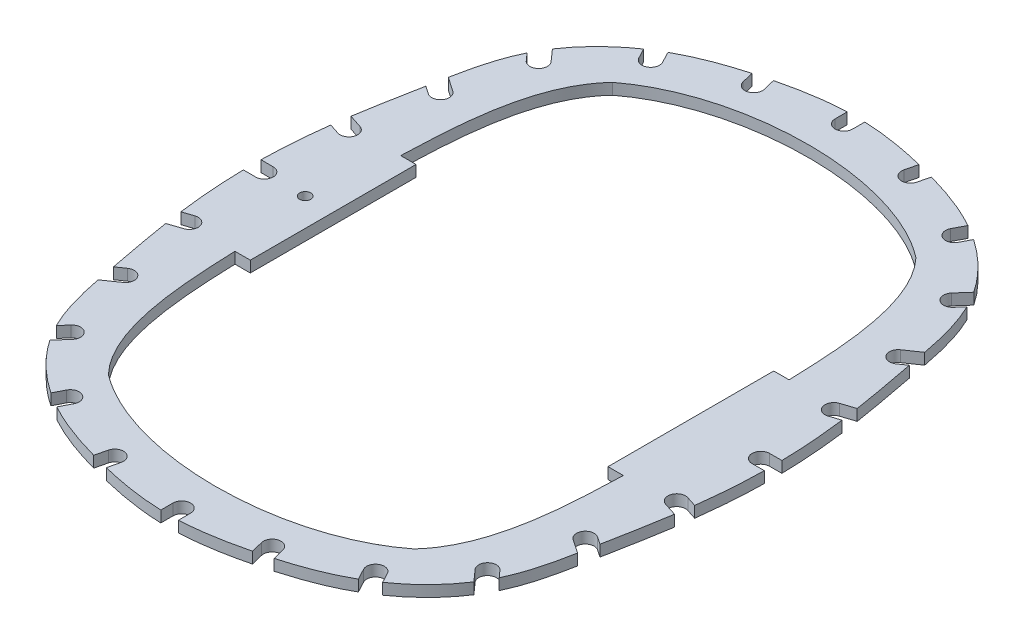
SolidWorks part; units mm, degrees
ref_plane "Front Plane" through (0, 0, 0) normal (0, 0, 1) x (1, 0, 0)
ref_plane "Top Plane" through (0, 0, 0) normal (0, 1, 0) x (1, 0, 0)
ref_plane "Right Plane" through (0, 0, 0) normal (1, 0, 0) x (0, 0, -1)
sketch "MainControlPoints" plane through (0, 0, 0) normal (0, 1, 0) x (1, 0, 0)
  line L1 (0, 188.5) -> (0, 0) construction
  line L2 (-44.5, 181.8105) -> (44.5, 181.8105) construction
  line L9 (-141, 0) -> (141, 0) construction
  line L10 (-86.25, 165.0195) -> (86.25, 165.0195) construction
  line L11 (-117.5, 132.6399) -> (117.5, 132.6399) construction
  line L12 (-130, 89.4108) -> (130, 89.4108) construction
  line L13 (-137.75, 45.0832) -> (137.75, 45.0832) construction
  spline S0 degree 3 poles (-44.8235, 182.8439) (0, 191.3281) (44.8235, 182.8439) (87.706, 168.1591) (121.8523, 134.6364) (129.8847, 89.1344) (138.6218, 45.2258) (142.1917, 0) (138.6218, -45.2258) (129.8847, -89.1344) (121.8523, -134.6364) (87.706, -168.1591) (44.8235, -182.8439) (0, -191.3281) (-44.8235, -182.8439) (-87.706, -168.1591) (-121.8523, -134.6364) (-129.8847, -89.1344) (-138.6218, -45.2258) (-142.1917, 0) (-138.6218, 45.2258) (-129.8847, 89.1344) (-121.8523, 134.6364) (-87.706, 168.1591) (-44.8235, 182.8439) (0, 191.3281) (44.8235, 182.8439) knots -0.124907 -0.083272 -0.041636 0 0.041636 0.083272 0.124907 0.166543 0.208179 0.25 0.291821 0.333457 0.375093 0.416728 0.458364 0.5 0.541636 0.583272 0.624907 0.666543 0.708179 0.75 0.791821 0.833457 0.875093 0.916728 0.958364 1 1.041636 1.083272 1.124907 only from (0, 188.5) to (0, 188.5)
  point P4 (0, 181.8105)
  point P7 (0, 0)
  point P8 (141, 0)
  point P9 (-141, 0)
  point P11 (44.5, 181.8105)
  point P14 (86.25, 165.0195)
  point P15 (0, 165.0195)
  point P16 (117.5, 132.6399)
  point P17 (130, 89.4108)
  point P18 (-44.5, 181.8105)
  point P19 (-86.25, 165.0195)
  point P20 (-117.5, 132.6399)
  point P23 (0, 132.6399)
  point P24 (137.75, 45.0832)
  point P25 (-130, 89.4108)
  point P26 (-137.75, 45.0832)
  point P27 (0, 188.5)
  point P30 (0, 89.4108)
  point P33 (0, 45.0832)
  point P34 (137.75, -45.0832)
  point P35 (130, -89.4108)
  point P36 (117.5, -132.6399)
  point P37 (86.25, -165.0195)
  point P38 (44.5, -181.8105)
  point P39 (0, -188.5)
  point P40 (-44.5, -181.8105)
  point P41 (-86.25, -165.0195)
  point P42 (-117.5, -132.6399)
  point P43 (-130, -89.4108)
  point P44 (-137.75, -45.0832)
  dimension "D3" = 282
  dimension "D2" = 188.5
  dimension "D5" = 45
  dimension "D6" = 45
  dimension "D1" = 89
  dimension "D4" = 172.5
  dimension "D7" = 45
  dimension "D8" = 235
  dimension "D9" = 45
  dimension "D10" = 260
  dimension "D11" = 45
  dimension "D12" = 275.5
ref_axis "Axis1" through (0, 0, -188.5) along (0, 1, 0)
ref_axis "Axis2" through (44.5, 0, -181.8105) along (0, 1, 0)
ref_axis "Axis3" through (86.25, 0, -165.0195) along (0, 1, 0)
ref_axis "Axis4" through (117.5, 0, -132.6399) along (0, 1, 0)
ref_axis "Axis5" through (130, 0, -89.4108) along (0, 1, 0)
ref_axis "Axis6" through (137.75, 0, -45.0832) along (0, 1, 0)
ref_axis "Axis7" through (141, 0, 0) along (0, 1, 0)
ref_axis "Axis8" through (137.75, 0, 45.0832) along (0, 1, 0)
ref_axis "Axis9" through (130, 0, 89.4108) along (0, 1, 0)
ref_axis "Axis10" through (117.5, 0, 132.6399) along (0, 1, 0)
ref_axis "Axis11" through (86.25, 0, 165.0195) along (0, 1, 0)
ref_axis "Axis12" through (44.5, 0, 181.8105) along (0, 1, 0)
ref_axis "Axis13" through (0, 0, 188.5) along (0, 1, 0)
ref_axis "Axis14" through (-44.5, 0, 181.8105) along (0, 1, 0)
ref_axis "Axis15" through (-86.25, 0, 165.0195) along (0, 1, 0)
ref_axis "Axis16" through (-117.5, 0, 132.6399) along (0, 1, 0)
ref_axis "Axis17" through (-130, 0, 89.4108) along (0, 1, 0)
ref_axis "Axis18" through (-137.75, 0, 45.0832) along (0, 1, 0)
ref_axis "Axis19" through (-141, 0, 0) along (0, 1, 0)
ref_axis "Axis20" through (-137.75, 0, -45.0832) along (0, 1, 0)
ref_axis "Axis21" through (-130, 0, -89.4108) along (0, 1, 0)
ref_axis "Axis22" through (-117.5, 0, -132.6399) along (0, 1, 0)
ref_axis "Axis23" through (-86.25, 0, -165.0195) along (0, 1, 0)
ref_axis "Axis24" through (-44.5, 0, -181.8105) along (0, 1, 0)
sketch "Sketch3" plane through (0, 0, 0) normal (0, 1, 0) x (1, 0, 0)
  spline S2 degree 3 poles (44.8235, 182.8439) (0, 191.3281) (-44.8235, 182.8439) (-87.706, 168.1591) (-121.8523, 134.6364) (-129.8847, 89.1344) (-138.6218, 45.2258) (-142.1917, 0) (-138.6218, -45.2258) (-129.8847, -89.1344) (-121.8523, -134.6364) (-87.706, -168.1591) (-44.8235, -182.8439) (0, -191.3281) (44.8235, -182.8439) (87.706, -168.1591) (121.8523, -134.6364) (129.8847, -89.1344) (138.6218, -45.2258) (142.1917, 0) (138.6218, 45.2258) (129.8847, 89.1344) (121.8523, 134.6364) (87.706, 168.1591) (44.8235, 182.8439) (0, 191.3281) (-44.8235, 182.8439) knots -0.124907 -0.083272 -0.041636 0 0.041636 0.083272 0.124907 0.166543 0.208179 0.25 0.291821 0.333457 0.375093 0.416728 0.458364 0.5 0.541636 0.583272 0.624907 0.666543 0.708179 0.75 0.791821 0.833457 0.875093 0.916728 0.958364 1 1.041636 1.083272 1.124907 only from (0, 188.5) to (0, 188.5)
  spline S3 degree 3 poles (44.8235, 182.8439) (0, 191.3281) (-44.8235, 182.8439) (-87.706, 168.1591) (-121.8523, 134.6364) (-129.8847, 89.1344) (-138.6218, 45.2258) (-142.1917, 0) (-138.6218, -45.2258) (-129.8847, -89.1344) (-121.8523, -134.6364) (-87.706, -168.1591) (-44.8235, -182.8439) (0, -191.3281) (44.8235, -182.8439) (87.706, -168.1591) (121.8523, -134.6364) (129.8847, -89.1344) (138.6218, -45.2258) (142.1917, 0) (138.6218, 45.2258) (129.8847, 89.1344) (121.8523, 134.6364) (87.706, 168.1591) (44.8235, 182.8439) (0, 191.3281) (-44.8235, 182.8439) knots -0.124907 -0.083272 -0.041636 0 0.041636 0.083272 0.124907 0.166543 0.208179 0.25 0.291821 0.333457 0.375093 0.416728 0.458364 0.5 0.541636 0.583272 0.624907 0.666543 0.708179 0.75 0.791821 0.833457 0.875093 0.916728 0.958364 1 1.041636 1.083272 1.124907 only from (0, 188.5) to (0, 188.5)
  dimension "D1" = 0
extrude "MainBody" add sketch "Sketch3" along normal blind 6.35
sketch "Sketch13" plane through (0, 6.35, 0) normal (0, 1, 0) x (1, 0, 0)
  spline S2 degree 3 poles (-0.0923, -195.5) (5.9061, -195.5) (11.7392, -195.085) (23.2981, -193.6453) (29.0237, -192.6199) (37.5559, -190.7615) (40.3905, -190.0886) (46.0447, -188.657) (48.8649, -187.9023) (53.0829, -186.6998) (54.4867, -186.2866) (57.2893, -185.4316) (58.6882, -184.9896) (62.8604, -183.6197) (65.6138, -182.6462) (73.7714, -179.5048) (79.0728, -177.1157) (86.7462, -172.933) (89.2575, -171.4385) (92.9463, -169.029) (94.1653, -168.1965) (96.5575, -166.4889) (97.7326, -165.6128) (101.1944, -162.9177) (103.4182, -161.032) (107.6923, -157.0772) (109.7427, -155.0081) (112.678, -151.7562) (113.633, -150.6474) (115.0284, -148.9451) (115.4873, -148.3711) (116.3925, -147.2097) (116.8393, -146.6213) (119.0306, -143.6582) (120.6466, -141.2209) (123.5916, -136.206) (124.9153, -133.6259) (127.2923, -128.3337) (128.3485, -125.623) (129.7723, -121.4785) (130.2202, -120.084) (131.0691, -117.272) (131.4694, -115.8571) (132.6042, -111.6095) (133.2755, -108.7656) (134.5145, -103.0626) (135.0819, -100.2036) (136.1775, -94.48) (136.707, -91.6156) (138.3251, -83.0265) (139.4215, -77.303) (141.5293, -65.8438) (142.5403, -60.108) (143.9035, -51.4821) (144.3323, -48.6031) (145.1247, -42.8358) (145.4885, -39.9475) (147.1362, -25.4811) (147.9101, -13.8294) (148.003, -0.6092) (148.0024, 0.8623) (147.9792, 3.8019) (147.9568, 5.2701) (147.8578, 9.6699) (147.7498, 12.5969) (147.3068, 21.3604) (146.8533, 27.1792) (145.6651, 38.7754) (144.9284, 44.5524) (143.2126, 56.0705) (142.2389, 61.8124) (140.1775, 73.2794) (139.0901, 79.0044) (137.4645, 87.5929) (136.9262, 90.4562) (135.8531, 96.1835) (135.3122, 99.0464) (133.5786, 107.6189) (132.2779, 113.3124) (130.1353, 120.3529) (129.6824, 121.7514) (128.7233, 124.5187) (128.2169, 125.8886) (126.6073, 129.9525) (125.4138, 132.6004) (122.7385, 137.7496) (121.2544, 140.2496) (118.8215, 143.8945) (117.9761, 145.0919) (116.2177, 147.4523) (115.3033, 148.6168) (112.4942, 152.0199) (110.5242, 154.1827) (106.4077, 158.3162) (104.2612, 160.2869) (99.8013, 164.0465) (97.4878, 165.8355) (93.8939, 168.384) (92.6724, 169.2128) (90.2027, 170.8151) (88.9554, 171.5879) (82.6598, 175.3171) (77.4348, 177.8708) (66.7035, 182.3362) (61.1969, 184.2476) (54.1978, 186.3725) (52.791, 186.7846) (49.9736, 187.5842) (48.5634, 187.9716) (44.3294, 189.1029) (41.5021, 189.818) (33.0032, 191.8167) (27.3144, 192.953) (15.8708, 194.6608) (10.1162, 195.2328) (1.4182, 195.5241) (-1.4925, 195.5238) (-7.3372, 195.3237) (-10.2708, 195.1267) (-14.6866, 194.6996) (-16.1609, 194.5352) (-19.0943, 194.1679) (-20.556, 193.9647) (-24.9277, 193.3015) (-27.824, 192.7881) (-36.4681, 191.071) (-42.1715, 189.6926) (-53.5026, 186.6371) (-59.1262, 184.9441) (-66.0624, 182.4605) (-67.445, 181.9454) (-70.1997, 180.8739) (-71.5737, 180.3168) (-75.6639, 178.5832) (-78.3432, 177.3468) (-83.5935, 174.6901) (-86.1644, 173.2698) (-91.1858, 170.2243) (-93.6357, 168.5985) (-97.2169, 166.0005) (-98.395, 165.108) (-100.7189, 163.2682) (-101.8655, 162.32) (-105.2234, 159.4186) (-107.3637, 157.4004) (-111.4418, 153.191) (-113.3796, 150.9998) (-117.0378, 146.4319) (-118.7583, 144.0551) (-121.1568, 140.3344) (-121.9259, 139.0681) (-123.0304, 137.1268) (-123.3898, 136.4736) (-124.087, 135.1618) (-124.4255, 134.5022) (-126.0692, 131.1868) (-127.2294, 128.4785) (-130.3408, 120.2205) (-131.9223, 114.5371) (-134.5909, 102.9918) (-135.6643, 97.1921) (-137.8355, 85.5987) (-138.9477, 79.8043) (-141.1029, 68.2094) (-142.1451, 62.4088) (-143.5618, 53.6948) (-144.0097, 50.788) (-144.8419, 44.9686) (-145.2255, 42.056) (-146.97, 27.4776) (-147.815, 15.7657) (-148.0521, -1.8942) (-147.9538, -7.7967) (-147.4225, -19.6316) (-146.9909, -25.5639) (-146.1143, -34.4827) (-145.7838, -37.4592) (-145.0527, -43.3941) (-144.6515, -46.3556) (-143.3516, -55.2244) (-142.36, -61.1163) (-140.253, -72.8796) (-139.1381, -78.7512) (-137.4708, -87.5593) (-136.9189, -90.496) (-135.8181, -96.3698) (-135.2627, -99.3053) (-133.4794, -108.0788) (-132.1352, -113.8842) (-129.4893, -122.4151) (-128.5024, -125.2292) (-126.8117, -129.3912) (-126.2131, -130.7686) (-125.2553, -132.818) (-124.9263, -133.498) (-124.2516, -134.843) (-123.9056, -135.5092) (-122.1306, -138.8075) (-120.5688, -141.343) (-117.1925, -146.2303) (-115.378, -148.582) (-111.5149, -153.1153) (-109.4647, -155.2983) (-105.1449, -159.494) (-102.9036, -161.4797) (-95.9543, -167.1259) (-91.0211, -170.4758) (-84.4967, -174.1698) (-83.1716, -174.8856) (-80.5028, -176.2632) (-79.1594, -176.925) (-75.1047, -178.8358) (-72.3686, -180.0105) (-64.0786, -183.2871) (-58.4429, -185.1422) (-49.8888, -187.6214) (-47.0211, -188.3984) (-41.2605, -189.8765) (-38.3664, -190.5739) (-32.5429, -191.862) (-29.6099, -192.4531) (-23.735, -193.4975) (-20.7901, -193.9515) (-14.8831, -194.699) (-11.9208, -194.9924) (-7.4624, -195.2928) (-5.9738, -195.3696) (-3.7367, -195.4473) (-2.6172, -195.4768) (-1.3092, -195.4942) (-0.6548, -195.4985) (-0.3742, -195.4995) (-0.1871, -195.4999) (-0.0923, -195.5) (5.9061, -195.5) (11.7392, -195.085) knots -0.000244 -0.000244 0 0 0.015625 0.015625 0.03125 0.03125 0.039063 0.039063 0.046875 0.046875 0.050781 0.050781 0.054688 0.054688 0.0625 0.0625 0.078125 0.078125 0.085938 0.085938 0.089844 0.089844 0.09375 0.09375 0.101563 0.101563 0.109375 0.109375 0.113281 0.113281 0.115234 0.115234 0.117188 0.117188 0.125 0.125 0.132813 0.132813 0.140625 0.140625 0.144531 0.144531 0.148438 0.148438 0.15625 0.15625 0.164063 0.164063 0.171875 0.171875 0.1875 0.1875 0.203125 0.203125 0.210938 0.210938 0.21875 0.21875 0.25 0.25 0.253906 0.253906 0.257813 0.257813 0.265625 0.265625 0.28125 0.28125 0.296875 0.296875 0.3125 0.3125 0.328125 0.328125 0.335938 0.335938 0.34375 0.34375 0.359375 0.359375 0.363281 0.363281 0.367188 0.367188 0.375 0.375 0.382813 0.382813 0.386719 0.386719 0.390625 0.390625 0.398438 0.398438 0.40625 0.40625 0.414063 0.414063 0.417969 0.417969 0.421875 0.421875 0.4375 0.4375 0.453125 0.453125 0.457031 0.457031 0.460938 0.460938 0.46875 0.46875 0.484375 0.484375 0.5 0.5 0.507813 0.507813 0.515625 0.515625 0.519531 0.519531 0.523438 0.523438 0.53125 0.53125 0.546875 0.546875 0.5625 0.5625 0.566406 0.566406 0.570313 0.570313 0.578125 0.578125 0.585938 0.585938 0.59375 0.59375 0.597656 0.597656 0.601563 0.601563 0.609375 0.609375 0.617188 0.617188 0.625 0.625 0.628906 0.628906 0.630859 0.630859 0.632813 0.632813 0.640625 0.640625 0.65625 0.65625 0.671875 0.671875 0.6875 0.6875 0.703125 0.703125 0.710937 0.710937 0.71875 0.71875 0.75 0.75 0.765625 0.765625 0.78125 0.78125 0.789062 0.789062 0.796875 0.796875 0.8125 0.8125 0.828125 0.828125 0.835937 0.835937 0.84375 0.84375 0.859375 0.859375 0.867187 0.867187 0.871094 0.871094 0.873047 0.873047 0.875 0.875 0.882812 0.882812 0.890625 0.890625 0.898437 0.898437 0.90625 0.90625 0.921875 0.921875 0.925781 0.925781 0.929687 0.929687 0.9375 0.9375 0.953125 0.953125 0.960937 0.960937 0.96875 0.96875 0.976562 0.976562 0.984375 0.984375 0.992188 0.992188 0.996094 0.996094 0.998047 0.999023 0.999512 0.999756 0.999756 1 1 1.015625 1.015625 1.03125 only from (0, -195.5) to (0, -195.5)
  spline S3 degree 3 poles (-0.0923, -195.5) (5.9061, -195.5) (11.7392, -195.085) (23.2981, -193.6453) (29.0237, -192.6199) (37.5559, -190.7615) (40.3905, -190.0886) (46.0447, -188.657) (48.8649, -187.9023) (53.0829, -186.6998) (54.4867, -186.2866) (57.2893, -185.4316) (58.6882, -184.9896) (62.8604, -183.6197) (65.6138, -182.6462) (73.7714, -179.5048) (79.0728, -177.1157) (86.7462, -172.933) (89.2575, -171.4385) (92.9463, -169.029) (94.1653, -168.1965) (96.5575, -166.4889) (97.7326, -165.6128) (101.1944, -162.9177) (103.4182, -161.032) (107.6923, -157.0772) (109.7427, -155.0081) (112.678, -151.7562) (113.633, -150.6474) (115.0284, -148.9451) (115.4873, -148.3711) (116.3925, -147.2097) (116.8393, -146.6213) (119.0306, -143.6582) (120.6466, -141.2209) (123.5916, -136.206) (124.9153, -133.6259) (127.2923, -128.3337) (128.3485, -125.623) (129.7723, -121.4785) (130.2202, -120.084) (131.0691, -117.272) (131.4694, -115.8571) (132.6042, -111.6095) (133.2755, -108.7656) (134.5145, -103.0626) (135.0819, -100.2036) (136.1775, -94.48) (136.707, -91.6156) (138.3251, -83.0265) (139.4215, -77.303) (141.5293, -65.8438) (142.5403, -60.108) (143.9035, -51.4821) (144.3323, -48.6031) (145.1247, -42.8358) (145.4885, -39.9475) (147.1362, -25.4811) (147.9101, -13.8294) (148.003, -0.6092) (148.0024, 0.8623) (147.9792, 3.8019) (147.9568, 5.2701) (147.8578, 9.6699) (147.7498, 12.5969) (147.3068, 21.3604) (146.8533, 27.1792) (145.6651, 38.7754) (144.9284, 44.5524) (143.2126, 56.0705) (142.2389, 61.8124) (140.1775, 73.2794) (139.0901, 79.0044) (137.4645, 87.5929) (136.9262, 90.4562) (135.8531, 96.1835) (135.3122, 99.0464) (133.5786, 107.6189) (132.2779, 113.3124) (130.1353, 120.3529) (129.6824, 121.7514) (128.7233, 124.5187) (128.2169, 125.8886) (126.6073, 129.9525) (125.4138, 132.6004) (122.7385, 137.7496) (121.2544, 140.2496) (118.8215, 143.8945) (117.9761, 145.0919) (116.2177, 147.4523) (115.3033, 148.6168) (112.4942, 152.0199) (110.5242, 154.1827) (106.4077, 158.3162) (104.2612, 160.2869) (99.8013, 164.0465) (97.4878, 165.8355) (93.8939, 168.384) (92.6724, 169.2128) (90.2027, 170.8151) (88.9554, 171.5879) (82.6598, 175.3171) (77.4348, 177.8708) (66.7035, 182.3362) (61.1969, 184.2476) (54.1978, 186.3725) (52.791, 186.7846) (49.9736, 187.5842) (48.5634, 187.9716) (44.3294, 189.1029) (41.5021, 189.818) (33.0032, 191.8167) (27.3144, 192.953) (15.8708, 194.6608) (10.1162, 195.2328) (1.4182, 195.5241) (-1.4925, 195.5238) (-7.3372, 195.3237) (-10.2708, 195.1267) (-14.6866, 194.6996) (-16.1609, 194.5352) (-19.0943, 194.1679) (-20.556, 193.9647) (-24.9277, 193.3015) (-27.824, 192.7881) (-36.4681, 191.071) (-42.1715, 189.6926) (-53.5026, 186.6371) (-59.1262, 184.9441) (-66.0624, 182.4605) (-67.445, 181.9454) (-70.1997, 180.8739) (-71.5737, 180.3168) (-75.6639, 178.5832) (-78.3432, 177.3468) (-83.5935, 174.6901) (-86.1644, 173.2698) (-91.1858, 170.2243) (-93.6357, 168.5985) (-97.2169, 166.0005) (-98.395, 165.108) (-100.7189, 163.2682) (-101.8655, 162.32) (-105.2234, 159.4186) (-107.3637, 157.4004) (-111.4418, 153.191) (-113.3796, 150.9998) (-117.0378, 146.4319) (-118.7583, 144.0551) (-121.1568, 140.3344) (-121.9259, 139.0681) (-123.0304, 137.1268) (-123.3898, 136.4736) (-124.087, 135.1618) (-124.4255, 134.5022) (-126.0692, 131.1868) (-127.2294, 128.4785) (-130.3408, 120.2205) (-131.9223, 114.5371) (-134.5909, 102.9918) (-135.6643, 97.1921) (-137.8355, 85.5987) (-138.9477, 79.8043) (-141.1029, 68.2094) (-142.1451, 62.4088) (-143.5618, 53.6948) (-144.0097, 50.788) (-144.8419, 44.9686) (-145.2255, 42.056) (-146.97, 27.4776) (-147.815, 15.7657) (-148.0521, -1.8942) (-147.9538, -7.7967) (-147.4225, -19.6316) (-146.9909, -25.5639) (-146.1143, -34.4827) (-145.7838, -37.4592) (-145.0527, -43.3941) (-144.6515, -46.3556) (-143.3516, -55.2244) (-142.36, -61.1163) (-140.253, -72.8796) (-139.1381, -78.7512) (-137.4708, -87.5593) (-136.9189, -90.496) (-135.8181, -96.3698) (-135.2627, -99.3053) (-133.4794, -108.0788) (-132.1352, -113.8842) (-129.4893, -122.4151) (-128.5024, -125.2292) (-126.8117, -129.3912) (-126.2131, -130.7686) (-125.2553, -132.818) (-124.9263, -133.498) (-124.2516, -134.843) (-123.9056, -135.5092) (-122.1306, -138.8075) (-120.5688, -141.343) (-117.1925, -146.2303) (-115.378, -148.582) (-111.5149, -153.1153) (-109.4647, -155.2983) (-105.1449, -159.494) (-102.9036, -161.4797) (-95.9543, -167.1259) (-91.0211, -170.4758) (-84.4967, -174.1698) (-83.1716, -174.8856) (-80.5028, -176.2632) (-79.1594, -176.925) (-75.1047, -178.8358) (-72.3686, -180.0105) (-64.0786, -183.2871) (-58.4429, -185.1422) (-49.8888, -187.6214) (-47.0211, -188.3984) (-41.2605, -189.8765) (-38.3664, -190.5739) (-32.5429, -191.862) (-29.6099, -192.4531) (-23.735, -193.4975) (-20.7901, -193.9515) (-14.8831, -194.699) (-11.9208, -194.9924) (-7.4624, -195.2928) (-5.9738, -195.3696) (-3.7367, -195.4473) (-2.6172, -195.4768) (-1.3092, -195.4942) (-0.6548, -195.4985) (-0.3742, -195.4995) (-0.1871, -195.4999) (-0.0923, -195.5) (5.9061, -195.5) (11.7392, -195.085) knots -0.000244 -0.000244 0 0 0.015625 0.015625 0.03125 0.03125 0.039063 0.039063 0.046875 0.046875 0.050781 0.050781 0.054688 0.054688 0.0625 0.0625 0.078125 0.078125 0.085938 0.085938 0.089844 0.089844 0.09375 0.09375 0.101563 0.101563 0.109375 0.109375 0.113281 0.113281 0.115234 0.115234 0.117188 0.117188 0.125 0.125 0.132813 0.132813 0.140625 0.140625 0.144531 0.144531 0.148438 0.148438 0.15625 0.15625 0.164063 0.164063 0.171875 0.171875 0.1875 0.1875 0.203125 0.203125 0.210938 0.210938 0.21875 0.21875 0.25 0.25 0.253906 0.253906 0.257813 0.257813 0.265625 0.265625 0.28125 0.28125 0.296875 0.296875 0.3125 0.3125 0.328125 0.328125 0.335938 0.335938 0.34375 0.34375 0.359375 0.359375 0.363281 0.363281 0.367188 0.367188 0.375 0.375 0.382813 0.382813 0.386719 0.386719 0.390625 0.390625 0.398438 0.398438 0.40625 0.40625 0.414063 0.414063 0.417969 0.417969 0.421875 0.421875 0.4375 0.4375 0.453125 0.453125 0.457031 0.457031 0.460938 0.460938 0.46875 0.46875 0.484375 0.484375 0.5 0.5 0.507813 0.507813 0.515625 0.515625 0.519531 0.519531 0.523438 0.523438 0.53125 0.53125 0.546875 0.546875 0.5625 0.5625 0.566406 0.566406 0.570313 0.570313 0.578125 0.578125 0.585938 0.585938 0.59375 0.59375 0.597656 0.597656 0.601563 0.601563 0.609375 0.609375 0.617188 0.617188 0.625 0.625 0.628906 0.628906 0.630859 0.630859 0.632813 0.632813 0.640625 0.640625 0.65625 0.65625 0.671875 0.671875 0.6875 0.6875 0.703125 0.703125 0.710937 0.710937 0.71875 0.71875 0.75 0.75 0.765625 0.765625 0.78125 0.78125 0.789062 0.789062 0.796875 0.796875 0.8125 0.8125 0.828125 0.828125 0.835937 0.835937 0.84375 0.84375 0.859375 0.859375 0.867187 0.867187 0.871094 0.871094 0.873047 0.873047 0.875 0.875 0.882812 0.882812 0.890625 0.890625 0.898437 0.898437 0.90625 0.90625 0.921875 0.921875 0.925781 0.925781 0.929687 0.929687 0.9375 0.9375 0.953125 0.953125 0.960937 0.960937 0.96875 0.96875 0.976562 0.976562 0.984375 0.984375 0.992188 0.992188 0.996094 0.996094 0.998047 0.999023 0.999512 0.999756 0.999756 1 1 1.015625 1.015625 1.03125 only from (0, -195.5) to (0, -195.5)
  dimension "D1" = 7
extrude "Extrude2Lip" add sketch "Sketch13" against normal up to surface (6.35 mm away)
sketch "Sketch14" plane through (0, 6.35, 0) normal (0, 1, 0) x (1, 0, 0)
  line L0 (-5, 188.5) -> (-5, 199.1798)
  line L1 (-5, 199.1798) -> (5, 199.1798)
  line L2 (5, 199.1798) -> (5, 188.5)
  line L9 (0, 188.5) -> (0, 199.1798) construction
  line L13 (-5, 188.5) -> (5, 188.5) construction
  line L20 (39.6434, 182.9992) -> (42.1824, 193.3728)
  line L21 (42.1824, 193.3728) -> (51.8957, 190.9953)
  line L22 (0, 0) -> (44.5, 181.8105) construction
  line L23 (0, 0) -> (86.25, 165.0195) construction
  line L24 (0, 0) -> (117.5, 132.6399) construction
  line L25 (0, 0) -> (130, 89.4108) construction
  line L26 (0, 0) -> (137.75, 45.0832) construction
  line L27 (0, 0) -> (141, 0.3435) construction
  line L28 (0, 0) -> (0, 188.5) construction
  line L29 (51.8957, 190.9953) -> (49.3566, 180.6217)
  line L30 (44.5, 181.8105) -> (47.039, 192.1841) construction
  line L31 (39.6434, 182.9992) -> (49.3566, 180.6217) construction
  line L32 (81.8188, 167.3355) -> (86.7658, 176.8005)
  line L33 (86.7658, 176.8005) -> (95.6283, 172.1684)
  line L34 (95.6283, 172.1684) -> (90.6812, 162.7034)
  line L35 (86.25, 165.0195) -> (91.197, 174.4844) construction
  line L36 (81.8188, 167.3355) -> (90.6812, 162.7034) construction
  line L37 (113.7573, 135.9554) -> (125.8891, 149.6503)
  line L38 (125.8891, 149.6503) -> (133.3744, 143.0193)
  line L39 (133.3744, 143.0193) -> (121.2427, 129.3244)
  line L40 (117.5, 132.6399) -> (129.6317, 146.3348) construction
  line L41 (113.7573, 135.9554) -> (121.2427, 129.3244) construction
  line L42 (127.1666, 93.5305) -> (142.2527, 103.9064)
  line L43 (142.2527, 103.9064) -> (147.9195, 95.667)
  line L44 (147.9195, 95.667) -> (132.8334, 85.2912)
  line L45 (130, 89.4108) -> (145.0861, 99.7867) construction
  line L46 (127.1666, 93.5305) -> (132.8334, 85.2912) construction
  line L47 (136.1948, 49.8352) -> (153.5963, 55.5304)
  line L48 (153.5963, 55.5304) -> (156.7067, 46.0265)
  line L49 (156.7067, 46.0265) -> (139.3052, 40.3312)
  line L50 (137.75, 45.0832) -> (155.1515, 50.7784) construction
  line L51 (136.1948, 49.8352) -> (139.3052, 40.3312) construction
  line L52 (140.9878, 5.3435) -> (159.2975, 5.3881)
  line L53 (159.2975, 5.3881) -> (159.3219, -4.6119)
  line L54 (159.3219, -4.6119) -> (141.0122, -4.6565)
  line L55 (141, 0.3435) -> (159.3097, 0.3881) construction
  line L56 (140.9878, 5.3435) -> (141.0122, -4.6565) construction
  line L57 (-140.9878, 5.3435) -> (-141.0122, -4.6565) construction
  line L58 (-141, 0.3435) -> (-159.3097, 0.3881) construction
  line L59 (-136.1948, 49.8352) -> (-139.3052, 40.3312) construction
  line L60 (-137.75, 45.0832) -> (-155.1515, 50.7784) construction
  line L61 (-127.1666, 93.5305) -> (-132.8334, 85.2912) construction
  line L62 (-130, 89.4108) -> (-145.0861, 99.7867) construction
  line L63 (-113.7573, 135.9554) -> (-121.2427, 129.3244) construction
  line L64 (-117.5, 132.6399) -> (-129.6317, 146.3348) construction
  line L65 (-81.8188, 167.3355) -> (-90.6812, 162.7034) construction
  line L66 (-86.25, 165.0195) -> (-91.197, 174.4844) construction
  line L67 (-39.6434, 182.9992) -> (-49.3566, 180.6217) construction
  line L68 (-44.5, 181.8105) -> (-47.039, 192.1841) construction
  line L69 (-159.3219, -4.6119) -> (-141.0122, -4.6565)
  line L70 (-159.2975, 5.3881) -> (-159.3219, -4.6119)
  line L71 (-140.9878, 5.3435) -> (-159.2975, 5.3881)
  line L72 (-156.7067, 46.0265) -> (-139.3052, 40.3312)
  line L73 (-153.5963, 55.5304) -> (-156.7067, 46.0265)
  line L74 (-136.1948, 49.8352) -> (-153.5963, 55.5304)
  line L75 (-147.9195, 95.667) -> (-132.8334, 85.2912)
  line L76 (-142.2527, 103.9064) -> (-147.9195, 95.667)
  line L77 (-127.1666, 93.5305) -> (-142.2527, 103.9064)
  line L78 (-133.3744, 143.0193) -> (-121.2427, 129.3244)
  line L79 (-125.8891, 149.6503) -> (-133.3744, 143.0193)
  line L80 (-113.7573, 135.9554) -> (-125.8891, 149.6503)
  line L81 (-95.6283, 172.1684) -> (-90.6812, 162.7034)
  line L82 (-86.7658, 176.8005) -> (-95.6283, 172.1684)
  line L83 (-81.8188, 167.3355) -> (-86.7658, 176.8005)
  line L84 (-51.8957, 190.9953) -> (-49.3566, 180.6217)
  line L85 (-42.1824, 193.3728) -> (-51.8957, 190.9953)
  line L86 (-39.6434, 182.9992) -> (-42.1824, 193.3728)
  line L87 (-43.6136, -182.0251) -> (-46.1021, -192.411) construction
  line L88 (-38.7512, -183.1902) -> (-48.476, -180.8601) construction
  line L89 (-85.4449, -165.4378) -> (-90.3457, -174.9267) construction
  line L90 (-81.0024, -167.7322) -> (-89.8874, -163.1433) construction
  line L91 (-116.8523, -133.2108) -> (-128.9172, -146.9647) construction
  line L92 (-113.0935, -136.508) -> (-120.6111, -129.9136) construction
  line L93 (-129.5628, -90.0432) -> (-144.5981, -100.4924) construction
  line L94 (-126.7093, -94.149) -> (-132.4163, -85.9374) construction
  line L95 (-137.5287, -45.7539) -> (-154.9022, -51.5338) construction
  line L96 (-135.9503, -50.4982) -> (-139.1071, -41.0095) construction
  line L97 (136.436, -49.171) -> (139.5001, -39.652) construction
  line L98 (137.968, -44.4115) -> (155.3971, -50.0219) construction
  line L99 (127.6208, -92.9098) -> (133.2474, -84.6429) construction
  line L100 (130.4341, -88.7763) -> (145.5706, -99.0786) construction
  line L101 (114.4184, -135.3995) -> (121.8714, -128.7321) construction
  line L102 (118.1449, -132.0658) -> (130.3432, -145.7014) construction
  line L103 (82.6331, -166.9349) -> (91.4729, -162.2596) construction
  line L104 (87.053, -164.5972) -> (92.0461, -174.038) construction
  line L105 (40.5346, -182.8038) -> (50.2361, -180.3791) construction
  line L106 (45.3853, -181.5915) -> (47.9749, -191.9526) construction
  line L107 (-4.0815, -188.5221) -> (5.9184, -188.4734) construction
  line L108 (0.9185, -188.4978) -> (0.9705, -199.1775) construction
  line L109 (-38.7512, -183.1902) -> (-41.2397, -193.576)
  line L110 (-41.2397, -193.576) -> (-50.9644, -191.2459)
  line L111 (-50.9644, -191.2459) -> (-48.476, -180.8601)
  line L112 (-81.0024, -167.7322) -> (-85.9033, -177.2212)
  line L113 (-85.9033, -177.2212) -> (-94.7882, -172.6323)
  line L114 (-94.7882, -172.6323) -> (-89.8874, -163.1433)
  line L115 (-113.0935, -136.508) -> (-125.1584, -150.2619)
  line L116 (-125.1584, -150.2619) -> (-132.676, -143.6675)
  line L117 (-132.676, -143.6675) -> (-120.6111, -129.9136)
  line L118 (-126.7093, -94.149) -> (-141.7447, -104.5983)
  line L119 (-141.7447, -104.5983) -> (-147.4516, -96.3866)
  line L120 (-147.4516, -96.3866) -> (-132.4163, -85.9374)
  line L121 (-135.9503, -50.4982) -> (-153.3239, -56.2781)
  line L122 (-153.3239, -56.2781) -> (-156.4806, -46.7895)
  line L123 (-156.4806, -46.7895) -> (-139.1071, -41.0095)
  line L124 (156.9292, -45.2624) -> (139.5001, -39.652)
  line L125 (153.865, -54.7813) -> (156.9292, -45.2624)
  line L126 (136.436, -49.171) -> (153.865, -54.7813)
  line L127 (148.3839, -94.9451) -> (133.2474, -84.6429)
  line L128 (142.7573, -103.212) -> (148.3839, -94.9451)
  line L129 (127.6208, -92.9098) -> (142.7573, -103.212)
  line L130 (134.0697, -142.3677) -> (121.8714, -128.7321)
  line L131 (126.6167, -149.0351) -> (134.0697, -142.3677)
  line L132 (114.4184, -135.3995) -> (126.6167, -149.0351)
  line L133 (96.466, -171.7004) -> (91.4729, -162.2596)
  line L134 (87.6262, -176.3756) -> (96.466, -171.7004)
  line L135 (82.6331, -166.9349) -> (87.6262, -176.3756)
  line L136 (52.8257, -190.7402) -> (50.2361, -180.3791)
  line L137 (43.1241, -193.1649) -> (52.8257, -190.7402)
  line L138 (40.5346, -182.8038) -> (43.1241, -193.1649)
  line L139 (5.9704, -199.1531) -> (5.9184, -188.4734)
  line L140 (-4.0294, -199.2018) -> (5.9704, -199.1531)
  line L141 (-4.0815, -188.5221) -> (-4.0294, -199.2018)
  arc A0 (-5, 188.5) -> (5, 188.5) centre (0, 188.5) ccw
  arc A1 (39.6434, 182.9992) -> (49.3566, 180.6217) centre (44.5, 181.8105) ccw
  arc A2 (81.8188, 167.3355) -> (90.6812, 162.7034) centre (86.25, 165.0195) ccw
  arc A3 (113.7573, 135.9554) -> (121.2427, 129.3244) centre (117.5, 132.6399) ccw
  arc A4 (127.1666, 93.5305) -> (132.8334, 85.2912) centre (130, 89.4108) ccw
  arc A5 (136.1948, 49.8352) -> (139.3052, 40.3312) centre (137.75, 45.0832) ccw
  arc A6 (140.9878, 5.3435) -> (141.0122, -4.6565) centre (141, 0.3435) ccw
  arc A7 (-140.9878, 5.3435) -> (-141.0122, -4.6565) centre (-141, 0.3435) cw
  arc A8 (-136.1948, 49.8352) -> (-139.3052, 40.3312) centre (-137.75, 45.0832) cw
  arc A9 (-127.1666, 93.5305) -> (-132.8334, 85.2912) centre (-130, 89.4108) cw
  arc A10 (-113.7573, 135.9554) -> (-121.2427, 129.3244) centre (-117.5, 132.6399) cw
  arc A11 (-81.8188, 167.3355) -> (-90.6812, 162.7034) centre (-86.25, 165.0195) cw
  arc A12 (-39.6434, 182.9992) -> (-49.3566, 180.6217) centre (-44.5, 181.8105) cw
  arc A13 (-38.7512, -183.1902) -> (-48.476, -180.8601) centre (-43.6136, -182.0251) ccw
  arc A14 (-81.0024, -167.7322) -> (-89.8874, -163.1433) centre (-85.4449, -165.4378) ccw
  arc A15 (-113.0935, -136.508) -> (-120.6111, -129.9136) centre (-116.8523, -133.2108) ccw
  arc A16 (-126.7093, -94.149) -> (-132.4163, -85.9374) centre (-129.5628, -90.0432) ccw
  arc A17 (-135.9503, -50.4982) -> (-139.1071, -41.0095) centre (-137.5287, -45.7539) ccw
  arc A18 (136.436, -49.171) -> (139.5001, -39.652) centre (137.968, -44.4115) cw
  arc A19 (127.6208, -92.9098) -> (133.2474, -84.6429) centre (130.4341, -88.7763) cw
  arc A20 (114.4184, -135.3995) -> (121.8714, -128.7321) centre (118.1449, -132.0658) cw
  arc A21 (82.6331, -166.9349) -> (91.4729, -162.2596) centre (87.053, -164.5972) cw
  arc A22 (40.5346, -182.8038) -> (50.2361, -180.3791) centre (45.3853, -181.5915) cw
  arc A23 (-4.0815, -188.5221) -> (5.9184, -188.4734) centre (0.9185, -188.4978) cw
  point P16 (44.5, 181.8105)
  dimension "D1" = 5
  dimension "D4" = 10
extrude "Slots" cut sketch "Sketch14" against normal up to next
ref_plane "MajorAxisPlane" through (0, 0, 0) normal (-1, 0, 0) x (0, 0, 1)
ref_plane "MinorAxisPlane" through (0, 0, 0) normal (0, 0, 1) x (1, 0, 0)
sketch "Sketch16" plane through (0, 6.35, 0) normal (0, 1, 0) x (1, 0, 0)
  line L1 (-97.5, -132.6399) -> (97.5, -132.6399)
  line L2 (-97.5, -132.6399) -> (-97.5, 132.6399)
  line L3 (-97.5, 132.6399) -> (97.5, 132.6399)
  line L4 (97.5, -132.6399) -> (97.5, 132.6399)
  line L5 (-97.5, -132.6399) -> (97.5, 132.6399) construction
  line L6 (-97.5, 132.6399) -> (97.5, -132.6399) construction
  line L7 (-117.5, 132.6399) -> (117.5, 132.6399) construction
  point P0 (0, 0)
  dimension "D1" = 20
extrude "OuterRidge" cut sketch "Sketch16" against normal through all
hole_wizard "#6 Clearance Hole1" positions "Sketch17" profile "Sketch18" hole size "#6" standard "ANSI Inch" end condition through all
sketch "Sketch17" plane through (0, 6.35, 0) normal (0, 1, 0) x (1, 0, 0)
  line L0 (0, 188.5) -> (0, 0) construction
  line L1 (-117.5, 132.6399) -> (117.5, 132.6399) construction
  line L2 (-97.5, 142.6399) -> (0, 142.6399) construction
  line L5 (0, 142.6399) -> (0, 132.4272) construction
  line L7 (-3.5008, 0) -> (3.5008, 0) construction
  line L8 (-130, 89.4108) -> (130, 89.4108) construction
  line L12 (-125.8803, 86.5774) -> (-97.5, 86.5774) construction
  line L13 (-97.5, 132.6399) -> (-97.5, -132.6399) construction
  line L18 (-136, 0.3313) -> (-97.5, 0) construction
  line L20 (0, 0) -> (0, -89.1534) construction
  arc A0 (-132.8334, 85.2912) -> (-127.1666, 93.5305) centre (-130, 89.4108) ccw construction
  arc A2 (-141.0122, -4.6565) -> (-140.9878, 5.3435) centre (-141, 0.3435) ccw construction
  point P16 (-48.75, 142.6399)
  point P33 (0, 142.6399)
  point P42 (-48.75, 142.6399)
  point P51 (48.75, -142.6399)
  point P52 (0, -142.6399)
  point P53 (-48.75, -142.6399)
  point P54 (-111.6902, 89.4108)
  point P56 (-116.75, 0.1657)
  point P83 (-111.6902, 86.5774)
  point P101 (-116.75, 0.1657)
  point P103 (-113.2269, -89.1534)
  point P114 (113.2269, -89.1534)
  point P115 (116.75, 0.1657)
  point P116 (111.6902, 89.4108)
  point P117 (48.75, 142.6399)
  dimension "D1" = 10
sketch "Sketch18" plane through (-48.75, 6.35, -142.6399) normal (1, 0, 0) x (0, 0, 1)
  line L0 (0, 0) -> (0, 6.35)
  line L1 (0, 6.35) -> (1.8986, 6.35)
  line L2 (1.8986, 6.35) -> (1.8986, 0)
  line L5 (1.8986, 0) -> (0, 0)
  line L11 (0, -6.35) -> (0, 107.95) construction
  dimension "Thru Hole Dia." = 3.7973
  dimension "Thru Hole Depth" = 6.35
sketch "Sketch19" plane through (0, 6.35, 0) normal (0, 1, 0) x (1, 0, 0)
  line L0 (-97.5, -132.6399) -> (97.5, -132.6399) construction
  line L1 (97.5, -132.6399) -> (97.5, 132.6399) construction
  line L2 (97.5, 132.6399) -> (-97.5, 132.6399) construction
  line L3 (-97.5, 132.6399) -> (-97.5, -132.6399) construction
  line L4 (-97.5, -132.6399) -> (97.5, -132.6399)
  line L5 (97.5, -132.6399) -> (97.5, 132.6399)
  line L6 (97.5, 132.6399) -> (-97.5, 132.6399)
  line L7 (-97.5, 132.6399) -> (-97.5, -132.6399)
  line L9 (-120.65, -168.275) -> (120.65, -168.275)
  line L10 (-120.65, -168.275) -> (-120.65, 168.275)
  line L11 (-120.65, 168.275) -> (120.65, 168.275)
  line L12 (120.65, -168.275) -> (120.65, 168.275)
  line L13 (-120.65, -168.275) -> (120.65, 168.275) construction
  line L14 (-120.65, 168.275) -> (120.65, -168.275) construction
  spline S0 degree 3 poles (-126.8552, 141.0397) (0, 180.1316) (126.8552, 141.0397) (117.1462, 0) (126.8552, -141.0397) (0, -180.1316) (-126.8552, -141.0397) (-117.1462, 0) (-126.8552, 141.0397) (0, 180.1316) (126.8552, 141.0397) knots -0.391165 -0.25 -0.108835 0 0.108835 0.25 0.391165 0.5 0.608835 0.75 0.891165 1 1.108835 1.25 1.391165 only from (0, 168.275) to (0, 168.275)
  point P2 (0, 0)
  dimension "D1" = 336.55
  dimension "D2" = 241.3
extrude "Cut-Extrude1" cut sketch "Sketch19" against normal up to surface (6.35 mm away) contours S0 L6 | S0 L7 L10 | S0 L12 L5 | S0 L4 region at (-107.9495, 6.35, 0) region at (0, 6.35, 147.314) region at (107.9495, 6.35, 0) region at (0, 6.35, -147.314) up to face at (-48.75, 0, -144.5385)
sketch "Sketch20" plane through (0, 6.35, 0) normal (0, 1, 0) x (1, 0, 0)
  line L0 (-120.65, -47.0717) -> (-120.65, 47.0717) construction
  line L1 (120.65, -47.0717) -> (120.65, 47.0717) construction
  line L2 (-120.65, -47.0717) -> (-120.65, 47.0717)
  line L3 (120.65, -47.0717) -> (120.65, 47.0717)
  line L4 (-120.65, 0) -> (-117.475, 0)
  line L5 (120.65, 47.0717) -> (107.95, 47.0717)
  line L6 (120.65, 47.0717) -> (120.65, -47.0717)
  line L7 (120.65, -47.0717) -> (107.95, -47.0717)
  line L8 (107.95, 47.0717) -> (107.95, -47.0717)
  line L9 (-120.65, 47.0717) -> (-107.95, 47.0717)
  line L10 (-120.65, 47.0717) -> (-120.65, -47.0717)
  line L11 (-120.65, -47.0717) -> (-107.95, -47.0717)
  line L12 (-107.95, 47.0717) -> (-107.95, -47.0717)
  circle A2 centre (-117.475, 0) radius 3.175
  spline S0 degree 3 poles (-126.8552, 141.0397) (0, 180.1316) (126.8552, 141.0397) (117.1462, 0) (126.8552, -141.0397) (0, -180.1316) (-126.8552, -141.0397) (-117.1462, 0) (-126.8552, 141.0397) (0, 180.1316) (126.8552, 141.0397) knots -0.391165 -0.25 -0.108835 0 0.108835 0.25 0.391165 0.5 0.608835 0.75 0.891165 1 1.108835 1.25 1.391165 only from (120.65, -47.0717) to (-120.65, -47.0717) construction
  spline S1 degree 3 poles (-126.8552, 141.0397) (0, 180.1316) (126.8552, 141.0397) (117.1462, 0) (126.8552, -141.0397) (0, -180.1316) (-126.8552, -141.0397) (-117.1462, 0) (-126.8552, 141.0397) (0, 180.1316) (126.8552, 141.0397) knots -0.391165 -0.25 -0.108835 0 0.108835 0.25 0.391165 0.5 0.608835 0.75 0.891165 1 1.108835 1.25 1.391165 only from (-120.65, 47.0717) to (120.65, 47.0717) construction
  spline S2 degree 3 poles (120.65, -47.0717) (119.8975, -80.7314) (111.2715, -145.842) (0, -180.1316) (-111.2715, -145.842) (-119.8975, -80.7314) (-120.65, -47.0717) knots 0.294081 0.294081 0.294081 0.294081 0.391165 0.5 0.608835 0.705919 0.705919 0.705919 0.705919
  spline S3 degree 3 poles (-120.65, 47.0717) (-119.8975, 80.7314) (-111.2715, 145.842) (-38.4753, 168.275) (0, 168.275) (38.4753, 168.275) (111.2715, 145.842) (119.8975, 80.7314) (120.65, 47.0717) knots 0.794081 0.794081 0.794081 0.794081 0.891165 1 1 1 1.108835 1.205919 1.205919 1.205919 1.205919
  dimension "D2" = 12.7
  dimension "D3" = 3.175
  dimension "D1" = 12.7
extrude "Boss-Extrude2" add sketch "Sketch20" against normal up to surface (6.35 mm away) contours L5 L8 L7 L3 | A2 L2 L11 L12 L9 | A2 region at (-117.475, 6.35, -3.0852) region at (-114.2136, 6.35, 0) region at (114.3, 6.35, 0) up to face at (0.2639, 0, -0.0319)
fillet "Fillet1" radius 10 4 edges at (-120.65, 3.175, 47.0717) (-120.65, 3.175, -47.0717) (120.65, 3.175, 47.0717) (120.65, 3.175, -47.0717)
sketch "Sketch21" plane through (-107.95, 0, 0) normal (1, 0, 0) x (0, 0, -1)
  line L4 (-47.0717, 0) -> (47.0717, 0)
  line L5 (47.0717, 0) -> (47.0717, 6.35)
  line L6 (47.0717, 6.35) -> (-47.0717, 6.35)
  line L7 (-47.0717, 6.35) -> (-47.0717, 0)
  line L8 (-47.0717, 0) -> (47.0717, 0)
  line L9 (47.0717, 0) -> (47.0717, 6.35)
  line L10 (47.0717, 6.35) -> (-47.0717, 6.35)
  line L11 (-47.0717, 6.35) -> (-47.0717, 0)
  dimension "D1" = 0
extrude "Boss-Extrude3" add sketch "Sketch21" along normal blind 6.35
sketch "Sketch22" plane through (107.95, 0, 0) normal (-1, 0, 0) x (0, 0, 1)
  line L4 (-47.0717, 6.35) -> (-47.0717, 0)
  line L5 (-47.0717, 0) -> (47.0717, 0)
  line L6 (47.0717, 0) -> (47.0717, 6.35)
  line L7 (47.0717, 6.35) -> (-47.0717, 6.35)
  line L8 (-47.0717, 6.35) -> (-47.0717, 0)
  line L9 (-47.0717, 0) -> (47.0717, 0)
  line L10 (47.0717, 0) -> (47.0717, 6.35)
  line L11 (47.0717, 6.35) -> (-47.0717, 6.35)
  dimension "D1" = 0
extrude "Boss-Extrude4" add sketch "Sketch22" along normal blind 6.35
sketch "Sketch24" plane through (0, 0, 0) normal (0, -1, 0) x (1, 0, 0)
  line L0 (86.25, -165.0195) -> (87.053, 164.5972)
  line L1 (-86.25, -165.0195) -> (-85.4449, 165.4378)
  line L2 (0, -183.5) -> (0.8941, 183.4978)
  arc A0 (110.303, 47.0717) -> (120.2917, 57.5466) centre (110.303, 57.0717) ccw construction
  arc A1 (-120.2917, 57.5466) -> (-110.303, 47.0717) centre (-110.303, 57.0717) ccw construction
  arc A2 (-110.303, -47.0717) -> (-120.2917, -57.5466) centre (-110.303, -57.0717) ccw construction
  arc A3 (120.2917, -57.5466) -> (110.303, -47.0717) centre (110.303, -57.0717) ccw construction
  arc A4 (110.303, 47.0717) -> (120.2917, 57.5466) centre (110.303, 57.0717) ccw
  arc A5 (-120.2917, 57.5466) -> (-110.303, 47.0717) centre (-110.303, 57.0717) ccw
  arc A6 (-110.303, -47.0717) -> (-120.2917, -57.5466) centre (-110.303, -57.0717) ccw
  arc A7 (120.2917, -57.5466) -> (110.303, -47.0717) centre (110.303, -57.0717) ccw
  arc A8 (82.6331, 166.9349) -> (91.4729, 162.2596) centre (87.053, 164.5972) ccw construction
  arc A10 (-81.8188, -167.3355) -> (-90.6812, -162.7034) centre (-86.25, -165.0195) ccw construction
  arc A11 (90.6812, -162.7034) -> (81.8188, -167.3355) centre (86.25, -165.0195) ccw construction
  arc A12 (82.6331, 166.9349) -> (91.4729, 162.2596) centre (87.053, 164.5972) ccw
  arc A13 (-89.8874, 163.1433) -> (-81.0024, 167.7322) centre (-85.4449, 165.4378) ccw construction
  arc A14 (-81.8188, -167.3355) -> (-90.6812, -162.7034) centre (-86.25, -165.0195) ccw
  arc A15 (90.6812, -162.7034) -> (81.8188, -167.3355) centre (86.25, -165.0195) ccw
  arc A16 (-89.8874, 163.1433) -> (-81.0024, 167.7322) centre (-85.4449, 165.4378) ccw
  arc A17 (5, -188.5) -> (-5, -188.5) centre (0, -188.5) ccw construction
  arc A18 (-4.0815, 188.5221) -> (5.9184, 188.4734) centre (0.9185, 188.4978) ccw construction
  spline S0 degree 3 poles (-126.8552, -141.0397) (0, -180.1316) (126.8552, -141.0397) (117.1462, 0) (126.8552, 141.0397) (0, 180.1316) (-126.8552, 141.0397) (-117.1462, 0) (-126.8552, -141.0397) (0, -180.1316) (126.8552, -141.0397) knots -0.391165 -0.25 -0.108835 0 0.108835 0.25 0.391165 0.5 0.608835 0.75 0.891165 1 1.108835 1.25 1.391165 only from (120.2917, 57.5466) to (-120.2917, 57.5466) construction
  spline S1 degree 3 poles (-126.8552, -141.0397) (0, -180.1316) (126.8552, -141.0397) (117.1462, 0) (126.8552, 141.0397) (0, 180.1316) (-126.8552, 141.0397) (-117.1462, 0) (-126.8552, -141.0397) (0, -180.1316) (126.8552, -141.0397) knots -0.391165 -0.25 -0.108835 0 0.108835 0.25 0.391165 0.5 0.608835 0.75 0.891165 1 1.108835 1.25 1.391165 only from (-120.2917, -57.5466) to (120.2917, -57.5466) construction
  spline S2 degree 3 poles (120.2917, 57.5466) (118.8888, 87.0598) (107.6756, 146.9501) (0, 180.1316) (-107.6756, 146.9501) (-118.8888, 87.0598) (-120.2917, 57.5466) knots 0.304253 0.304253 0.304253 0.304253 0.391165 0.5 0.608835 0.695747 0.695747 0.695747 0.695747
  spline S3 degree 3 poles (-120.2917, -57.5466) (-118.8888, -87.0598) (-107.6756, -146.9501) (-38.4753, -168.275) (0, -168.275) (38.4753, -168.275) (107.6756, -146.9501) (118.8888, -87.0598) (120.2917, -57.5466) knots 0.804253 0.804253 0.804253 0.804253 0.891165 1 1 1 1.108835 1.195747 1.195747 1.195747 1.195747
  spline S4 degree 3 poles (-104.7714, -157.2822) (0.0595, -173.5174) (104.8369, -157.2155) (111.4003, -44.0208) (111.2085, 43.8096) (105.4527, 156.652) (0.8884, 173.5174) (-104.1512, 157.8362) (-111.5237, 44.265) (-111.3327, -44.0546) (-104.7714, -157.2822) (0.0595, -173.5174) (104.8369, -157.2155) knots -0.299895 -0.200161 -0.095126 0 0.095183 0.200106 0.299841 0.404028 0.499248 0.594341 0.700105 0.799839 0.904874 1 1.095183 1.200106 1.299841 only from (0.0371, -168.275) to (0.0371, -168.275)
extrude "Boss-Extrude6" add sketch "Sketch24" against normal up to surface (6.35 mm away) contours S4 S3 A7 | S4 A6 S3 | S4 S2 A5 | S4 A4 S2 region at (110.5261, 0, -87.1428) region at (110.7071, 0, 86.6906) region at (-110.4878, 0, -87.2198) region at (-110.3043, 0, 87.6671) up to face at (0.2641, 6.35, -0.032)
extrude "Cut-Extrude3" cut sketch "Sketch20<4>" against normal up to surface (6.35 mm away) contours A2 region at (-117.475, 6.35, -3.0852) up to face at (0.134, 0, -0.0009)
sketch "Sketch20<4>" plane through (0, 6.35, 0) normal (0, 1, 0) x (1, 0, 0) same geometry as "Sketch20"
equation "\"MajorAxis\"= 377mm"
equation "\"MinorAxis\"= 282mm"
equation "\"MajorDiagonal\"= 353mm"
equation "\"SlotSpacing\"= 45mm"
equation "\"SlotRadius\"=5"
equation "\"D3@MainControlPoints\" = \"MinorAxis\""
equation "\"D2@MainControlPoints\" = \"MajorAxis\" / 2"
equation "\"D5@MainControlPoints\" = \"SlotSpacing\""
equation "\"D7@MainControlPoints\" = \"SlotSpacing\""
equation "\"D9@MainControlPoints\" = \"SlotSpacing\""
equation "\"D11@MainControlPoints\" = \"SlotSpacing\""
equation "\"D1@Sketch14\"=\"SlotRadius\""
equation "\"D4@Sketch14\"=\"SlotRadius\" * 2"
equation "\"Pt2LipEdge\"=7"
equation "\"D1@Sketch13\"=\"Pt2LipEdge\""
equation "\"OuterRidgeWidth\"=113.618"
